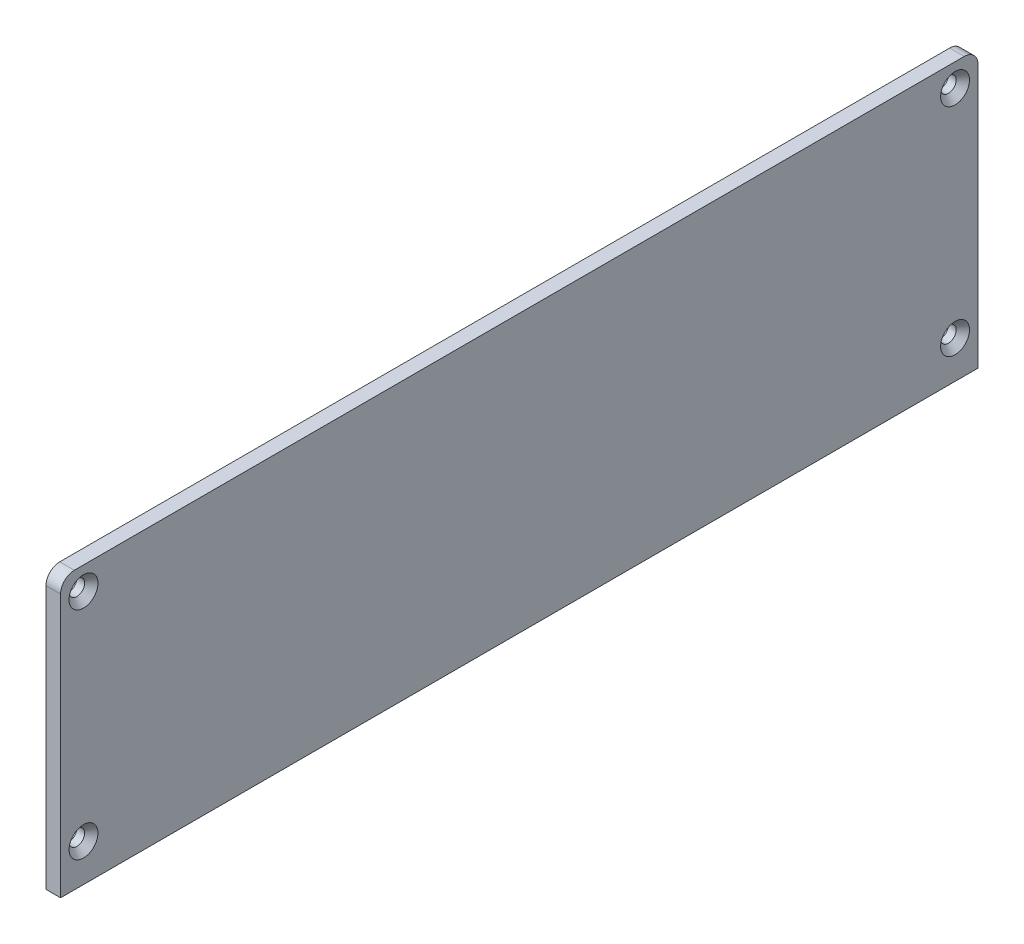
SolidWorks part; units mm, degrees
material "Garolite (G-10/FR4)"
ref_plane "Front Plane" through (0, 0, 0) normal (0, 0, 1) x (1, 0, 0)
ref_plane "Top Plane" through (0, 0, 0) normal (0, 1, 0) x (1, 0, 0)
ref_plane "Right Plane" through (0, 0, 0) normal (1, 0, 0) x (0, 0, -1)
sketch "Sketch1" plane through (0, 0, 0) normal (1, 0, 0) x (0, 0, -1)
  line L1 (-100, 0) -> (100, 0)
  line L2 (100, 0) -> (100, 57.35)
  line L3 (-100, 0) -> (-100, 57.35)
  line L4 (97, 60.35) -> (-97, 60.35)
  arc A0 (100, 57.35) -> (97, 60.35) centre (97, 57.35) ccw
  arc A1 (-97, 60.35) -> (-100, 57.35) centre (-97, 57.35) ccw
  dimension "D2" = 3
  dimension "D1" = 200
  dimension "D3" = 60.35
extrude "Boss-Extrude1" add sketch "Sketch1" along normal blind 3.175
hole_wizard "CSK for M3 Flat Head Machine Screw1" positions "Sketch3" profile "Sketch2" countersink size "M3" standard "Ansi Metric" end condition through all
sketch "Sketch3" plane through (3.175, 0, 0) normal (1, 0, 0) x (0, 0, -1)
  line L0 (-95, 0) -> (-95, 55.35) construction
  line L1 (-100, 0) -> (100, 0) construction
  line L3 (-100, 57.35) -> (-100, 0) construction
  line L4 (97, 60.35) -> (-97, 60.35) construction
  point P0 (-95, 8.175)
  point P1 (-95, 55.35)
  dimension "D1" = 5
  dimension "D2" = 8.175
  dimension "D3" = 5
sketch "Sketch2" plane through (3.175, 8.175, 95) normal (0, 1, 0) x (0, 0, -1)
  line L0 (0, 0) -> (0, 3.175)
  line L1 (0, 3.175) -> (1.7, 3.175)
  line L2 (1.7, 3.175) -> (1.7, 1.45)
  line L3 (1.7, 1.45) -> (3.15, 0)
  line L5 (3.15, 0) -> (0, 0)
  line L6 (-1.7, 1.45) -> (-3.15, 0) construction
  line L11 (0, -6.35) -> (0, 107.95) construction
  dimension "Thru Hole Dia." = 3.4
  dimension "Thru Hole Depth" = 3.175
  dimension "Near C'Sink Dia." = 6.3
  dimension "Near C'Sink Angle" = 90
mirror "Mirror1" about plane through (0, 0, 0) normal (0, 0, 1) of "CSK for M3 Flat Head Machine Screw1"
